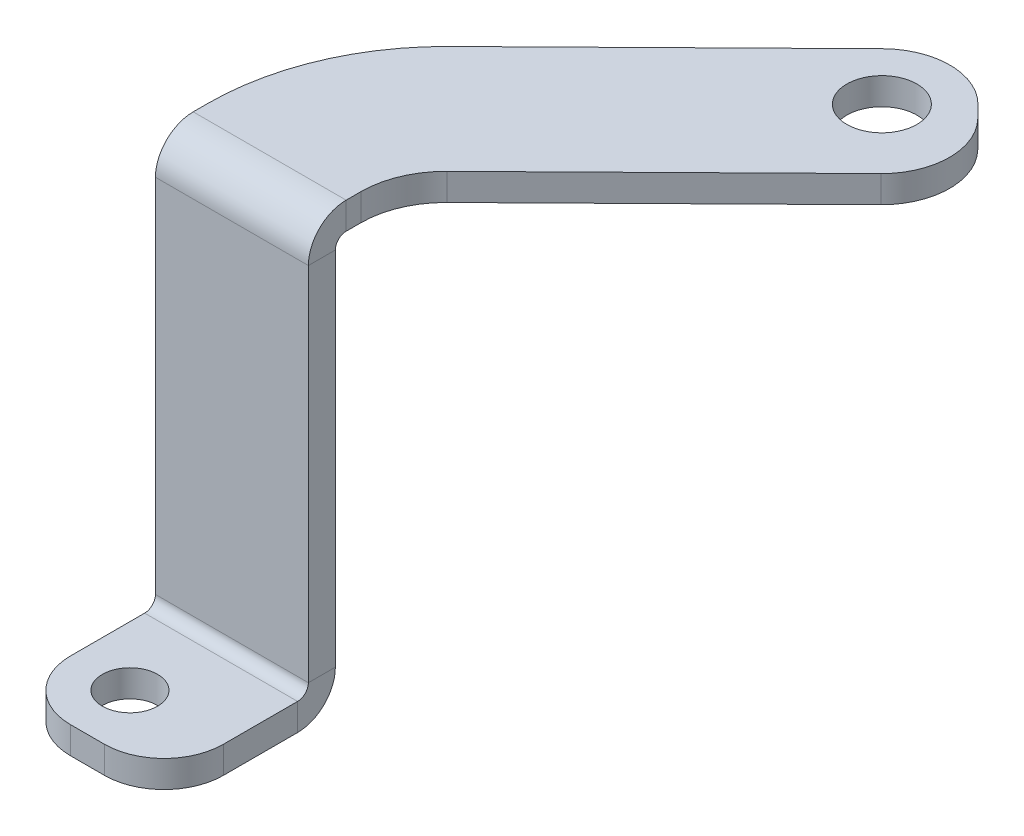
SolidWorks part; units mm, degrees
note: The reader was unsure of these and kept them because the rebuilt part matched: thickness of "Base-Flange1", "Edge-Flange1", "Edge-Flange2", "Sheet-Metal1", "Sheet-Metal2", "Sheet-Metal3", "Sheet-Metal4"; flange length of "Edge-Flange1", "Edge-Flange2".
material "Copper"
ref_plane "Front Plane" through (0, 0, 0) normal (0, 0, 1) x (1, 0, 0)
ref_plane "Top Plane" through (0, 0, 0) normal (0, 1, 0) x (1, 0, 0)
ref_plane "Right Plane" through (0, 0, 0) normal (1, 0, 0) x (0, 0, -1)
sketch "Sketch1" plane through (0, 0, 0) normal (0, 1, 0) x (1, 0, 0)
  line L0 (-7, 10) -> (-7, 0)
  line L2 (11, 10) -> (-7, 10)
  line L3 (0, -7) -> (4, -7)
  line L4 (11, 0) -> (11, 10)
  circle A0 centre (0, 0) radius 3.25
  arc A1 (-7, 0) -> (0, -7) centre (0, 0) ccw
  arc A2 (4, -7) -> (11, 0) centre (4, 0) ccw
  dimension "D1" = 6.5
  dimension "D2" = 7
  dimension "D4" = 18
  dimension "D3" = 10
base flange "Base-Flange1" sketch "Sketch1" thickness 3.175 reverse thickness direction no parameters "D1"=1.27
edge flange "Edge-Flange1" sketch "Sketch8" flange angle 90 flange length 48.2375 flange position material outside bend radius 1.27 thickness 3.175 relief rectangular parameters "D1"=0.7366, "D6"=10
sketch "Sketch8" plane through (0, 0, -10) normal (0, 0, -1) x (-1, 0, 0)
  line L0 (-11, 0) -> (7, 0) construction
  line L1 (-11, 0) -> (7, 0)
  line L2 (-11, 0) -> (-11, 45.0625)
  line L3 (-11, 45.0625) -> (7, 45.0625)
  line L4 (7, 45.0625) -> (7, 0)
  line L5 (-25.25, 45.0625) -> (-40.25, 45.0625) construction
bend "EdgeBend1" bend radius 1.27 bend angle 90 parameters "D5"=1
edge flange "Edge-Flange2" sketch "Sketch11" flange angle 90 flange length 6.175 flange position material outside bend radius 1.27 thickness 3.175 relief rectangular parameters "D1"=0.7366, "D6"=10
sketch "Sketch11" plane through (0, 45.0625, -13.175) normal (0, 1, 0) x (1, 0, 0)
  line L0 (-7, 0) -> (11, 0) construction
  line L1 (-7, 0) -> (11, 0)
  line L2 (-7, 0) -> (-7, 3)
  line L4 (11, 3) -> (11, 0)
  line L7 (-7, 3) -> (11, 3)
  dimension "D1" = 3
bend "EdgeBend2" bend radius 1.27 bend angle 90 parameters "D5"=2
sketch "Sketch12" plane through (0, 48.2375, 0) normal (0, 1, 0) x (1, 0, 0)
  line L0 (11, 16.175) -> (-7, 16.175)
  line L1 (1.3794, 36.1508) -> (27.1441, 61.4574)
  line L2 (39.7573, 48.6158) -> (13.9926, 23.3092)
  line L3 (11, 14.445) -> (11, 16.175) construction
  line L4 (-7, 16.175) -> (-7, 14.445) construction
  line L5 (38.4574, 61.3559) -> (39.8588, 59.929)
  arc A0 (-7, 16.175) -> (1.3794, 36.1508) centre (21, 16.175) cw
  arc A2 (13.9926, 23.3092) -> (11, 16.175) centre (21, 16.175) ccw
  circle A5 centre (32.75, 55.75) radius 4.125
  arc A6 (27.1441, 61.4574) -> (38.4574, 61.3559) centre (32.75, 55.75) cw
  arc A7 (39.8588, 59.929) -> (39.7573, 48.6158) centre (34.1515, 54.3232) cw
  dimension "D1" = 8.25
  dimension "D2" = 8
  dimension "D3" = 10
extrude "Boss-Extrude1" add sketch "Sketch12" against normal blind 3.175
sketch "Bend-Lines1" [suppressed] plane through (0, 0, 0) normal (0, 1, 0) x (1, 0, 0)
sketch "Bounding-Box1" [suppressed] plane through (0, 0, 0) normal (0, 1, 0) x (1, 0, 0)
sheet metal parameters "Sheet-Metal1" thickness 3.175 parameters "D1"=0.7366, "D7"=2
flat pattern "Flat-Pattern1" [suppressed]
sketch "Bend-Lines2" plane through (0, 0, 0) normal (0, 1, 0) x (1, 0, 0)
sketch3d "Bounding-Box2" [suppressed]
  line L0 (7, 12.5, 0) -> (7, -7, 0) construction
  line L1 (-7, 12.5, 0) -> (-7, -7, 0) construction
  line L2 (7, 12.5, 0) -> (-7, 12.5, 0) construction
  line L3 (7, -7, 0) -> (-7, -7, 0) construction
sheet metal parameters "Sheet-Metal2" thickness 3.175 parameters "D1"=0.7366, "D7"=2
flat pattern "Flat-Pattern1"
sketch "Bend-Lines2" plane through (0, 0, 0) normal (0, 1, 0) x (1, 0, 0)
  line L0 (7, 13.1273) -> (-7, 13.1273) construction
  line L1 (7, 13.1273) -> (-7, 13.1273) construction
sketch3d "Bounding-Box2" [suppressed]
  line L0 (7, 56.8171, 0) -> (7, -7, 0) construction
  line L1 (-7, 56.8171, 0) -> (-7, -7, 0) construction
  line L2 (7, 56.8171, 0) -> (-7, 56.8171, 0) construction
  line L3 (7, -7, 0) -> (-7, -7, 0) construction
bend of the flat pattern "Flatten-<EdgeBend1>1"
sheet metal parameters "Sheet-Metal3" thickness 3.175 parameters "D1"=0.7366, "D7"=2
flat pattern "Flat-Pattern1"
sketch "Bend-Lines2" plane through (0, 0, 0) normal (0, 1, 0) x (1, 0, 0)
  line L0 (7, 13.1273) -> (-7, 13.1273) construction
  line L1 (7, 13.1273) -> (-7, 13.1273) construction
  line L2 (7, 57.4445) -> (-7, 57.4445) construction
  line L3 (7, 57.4445) -> (-7, 57.4445) construction
sketch3d "Bounding-Box2" [suppressed]
  line L0 (7, 61.0718, 0) -> (7, -7, 0) construction
  line L1 (-7, 61.0718, 0) -> (-7, -7, 0) construction
  line L2 (7, 61.0718, 0) -> (-7, 61.0718, 0) construction
  line L3 (7, -7, 0) -> (-7, -7, 0) construction
bend of the flat pattern "Flatten-<EdgeBend1>1"
bend of the flat pattern "Flatten-<EdgeBend2>1"
sheet metal parameters "Sheet-Metal4" thickness 3.175 parameters "D1"=0.7366, "D7"=2
flat pattern "Flat-Pattern1"
sketch "Bend-Lines2" plane through (0, 0, 0) normal (0, 1, 0) x (1, 0, 0)
  line L0 (11, 10.5753) -> (-7, 10.5753) construction
  line L1 (11, 10.5753) -> (-7, 10.5753) construction
  line L2 (11, 56.7884) -> (-7, 56.7884) construction
  line L3 (11, 56.7884) -> (-7, 56.7884) construction
sketch3d "Bounding-Box2" [suppressed]
  line L0 (44.4765, 104.6163, 0) -> (8.195, -9.938, 0) construction
  line L1 (9.185, 115.7938, 0) -> (-27.0965, 1.2395, 0) construction
  line L2 (44.4765, 104.6163, 0) -> (9.185, 115.7938, 0) construction
  line L3 (8.195, -9.938, 0) -> (-27.0965, 1.2395, 0) construction
bend of the flat pattern "Flatten-<EdgeBend1>1"
bend of the flat pattern "Flatten-<EdgeBend2>1"
